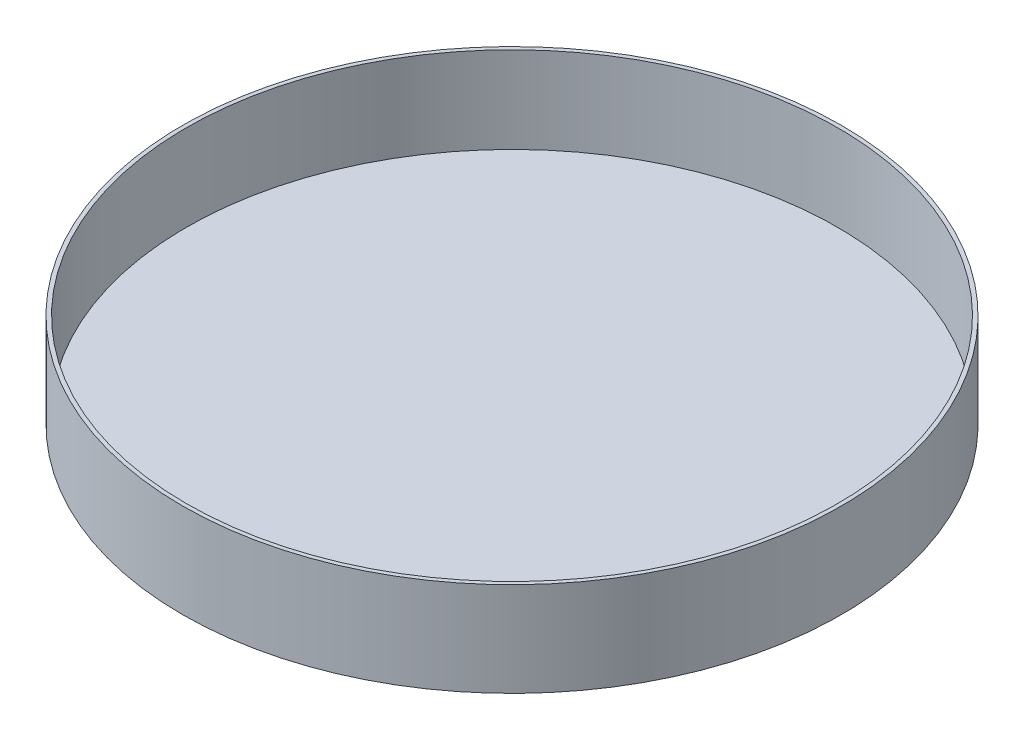
SolidWorks part; units mm, degrees
ref_plane "Front Plane" through (0, 0, 0) normal (0, 0, 1) x (1, 0, 0)
ref_plane "Top Plane" through (0, 0, 0) normal (0, 1, 0) x (1, 0, 0)
ref_plane "Right Plane" through (0, 0, 0) normal (1, 0, 0) x (0, 0, -1)
sketch "Sketch1" plane through (0, 0, 0) normal (0, 1, 0) x (1, 0, 0)
  circle A0 centre (0, 0) radius 266.7
extrude "Boss-Extrude1" add sketch "Sketch1" along normal blind 76.2
sketch "Sketch2" plane through (0, 76.2, 0) normal (0, 1, 0) x (1, 0, 0)
  circle A0 centre (0, 0) radius 263.525
extrude "Cut-Extrude1" cut sketch "Sketch2" against normal blind 69.85
